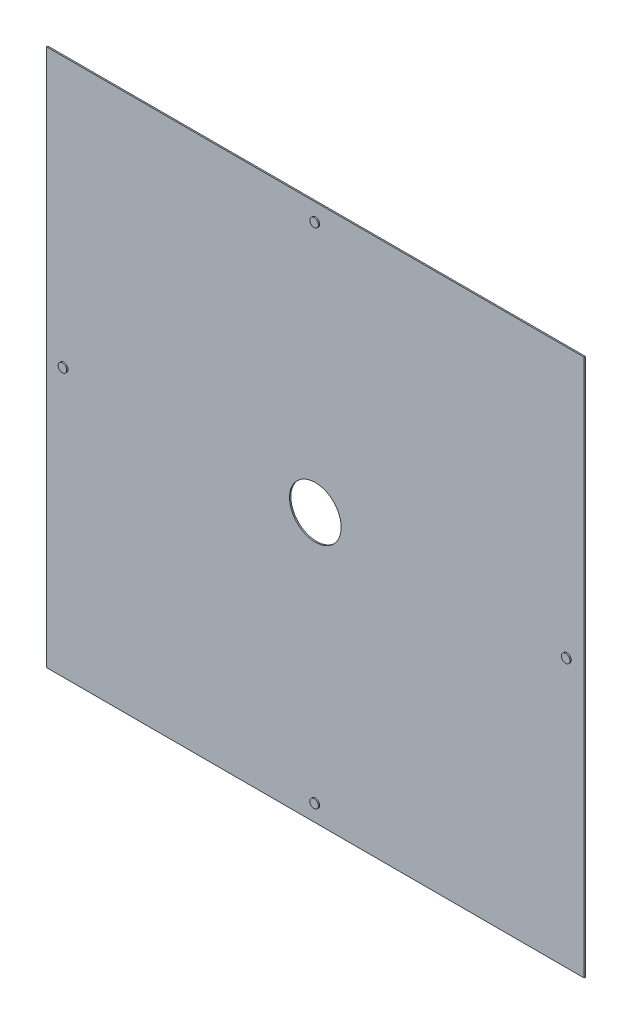
SolidWorks part; units mm, degrees
ref_plane "Front" through (0, 0, 0) normal (0, 0, 1) x (1, 0, 0)
ref_plane "Top" through (0, 0, 0) normal (0, 1, 0) x (1, 0, 0)
ref_plane "Right" through (0, 0, 0) normal (1, 0, 0) x (0, 0, -1)
sketch "Sketch2" plane through (0, 0, 0) normal (0, 0, 1) x (1, 0, 0)
  line L1 (-312.5, 312.5) -> (312.5, 312.5)
  line L2 (-312.5, 312.5) -> (-312.5, -312.5)
  line L3 (-312.5, -312.5) -> (312.5, -312.5)
  line L4 (312.5, 312.5) -> (312.5, -312.5)
  line L5 (-312.5, 312.5) -> (312.5, -312.5) construction
  line L6 (-312.5, -312.5) -> (312.5, 312.5) construction
  circle A0 centre (0, 0) radius 30
  point P0 (0, 0)
  dimension "D3" = 60
  dimension "D1" = 625
  dimension "D2" = 625
extrude "Boss-Extrude1" add sketch "Sketch2" along normal blind 1.5
sketch "Sketch3" plane through (0, 0, 1.5) normal (0, 0, 1) x (1, 0, 0)
  line L0 (-64.0866, 0) -> (74.0741, 0) construction
  line L1 (0, 80.7324) -> (0, -70.7449) construction
  line L2 (312.5, 312.5) -> (-312.5, 312.5) construction
  line L3 (312.5, -312.5) -> (312.5, 312.5) construction
  line L4 (-312.5, 312.5) -> (-312.5, -312.5) construction
  circle A0 centre (0, 292.5) radius 5
  circle A1 centre (-292.5, 0) radius 5
  circle A2 centre (0, -292.5) radius 5
  circle A3 centre (292.5, 0) radius 5
  dimension "D1" = 10
  dimension "D4" = 10
  dimension "D2" = 20
  dimension "D3" = 312.5
  dimension "D5" = 20
  dimension "D6" = 312.5
extrude "Boss-Extrude2" add sketch "Sketch3" along normal blind 1.5
